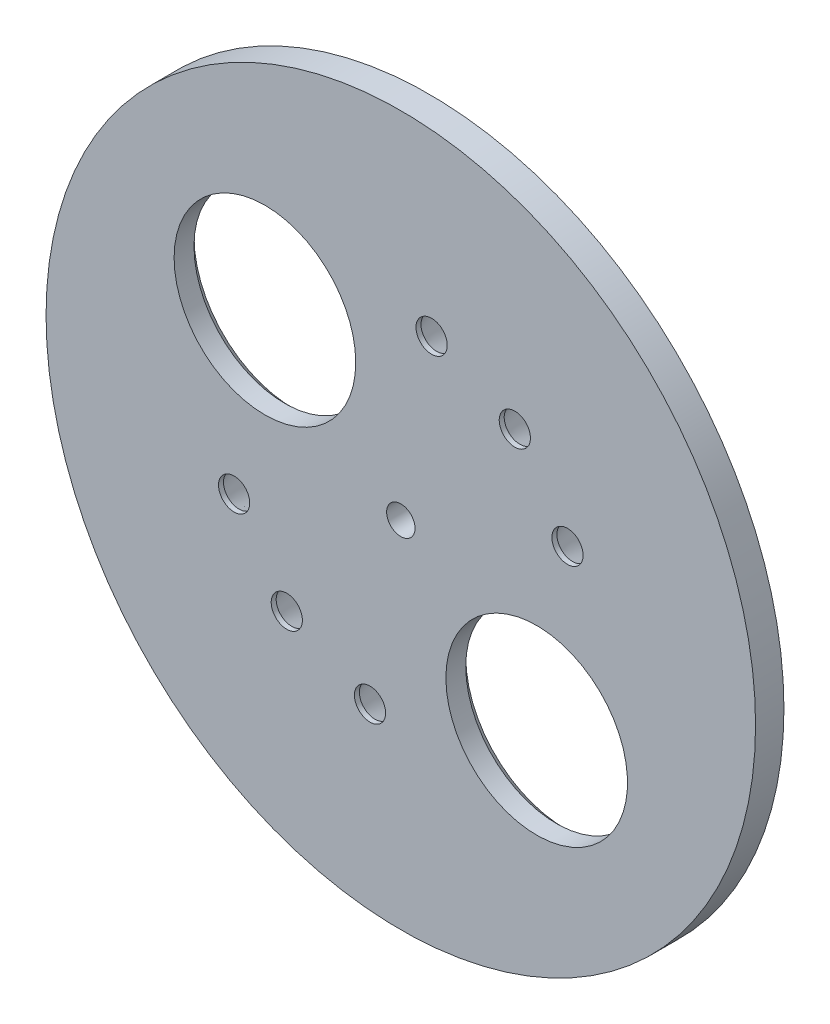
SolidWorks part; units mm, degrees
material "Pine"
ref_plane "Front Plane" through (0, 0, 0) normal (0, 0, 1) x (1, 0, 0)
ref_plane "Top Plane" through (0, 0, 0) normal (0, 1, 0) x (1, 0, 0)
ref_plane "Right Plane" through (0, 0, 0) normal (1, 0, 0) x (0, 0, -1)
sketch "Sketch1" plane through (0, 0, 0) normal (0, 0, 1) x (1, 0, 0)
  circle A0 centre (0, 0) radius 125
  point P2 (-48.2505, -61.8627)
  dimension "D1" = 250
extrude "Boss-Extrude1" add sketch "Sketch1" along normal blind 10
sketch "Sketch2" plane through (0, 0, 0) normal (0, 0, -1) x (-1, 0, 0)
  line L0 (0, 0) -> (-95.7556, -80.3485) construction
  line L1 (0, 0) -> (21.706, -123.101) construction
  line L2 (0, 0) -> (80.3485, -95.7556) construction
  line L3 (0, 0) -> (125, 0) construction
  line L4 (0, 0) -> (117.4616, -42.7525) construction
  circle A0 centre (0, 0) radius 5
  circle A1 centre (-47.8778, -40.1742) radius 32
  circle A2 centre (10.853, -61.5505) radius 5.5
  circle A3 centre (40.1742, -47.8778) radius 5.5
  circle A4 centre (0, 0) radius 125 construction
  circle A5 centre (58.7308, -21.3763) radius 5.5
  dimension "D1" = 10
  dimension "D2" = 64
  dimension "D3" = 11
  dimension "D4" = 140
  dimension "D5" = 60
  dimension "D6" = 30
  dimension "D7" = 30
extrude "Cut-Extrude1" cut sketch "Sketch2" against normal blind 10
chamfer "Chamfer1" distance 3 angle 45 1 edges at (15.8778, -40.1742, 0)
chamfer "Chamfer2" distance 3 angle 70 3 edges at (-64.2308, -21.3763, 0) (-45.6742, -47.8778, 0) (-16.353, -61.5505, 0) first distance on face at (82.8778, -40.1742, 0)
ref_axis "Axis1" through (0, 0, 10) along (0, 0, -1)
pattern_circular "CirPattern1" count 2 over 360 about axis through (0, 0, 10) along (0, 0, -1) of "Cut-Extrude1", "Chamfer2", "Chamfer1"
